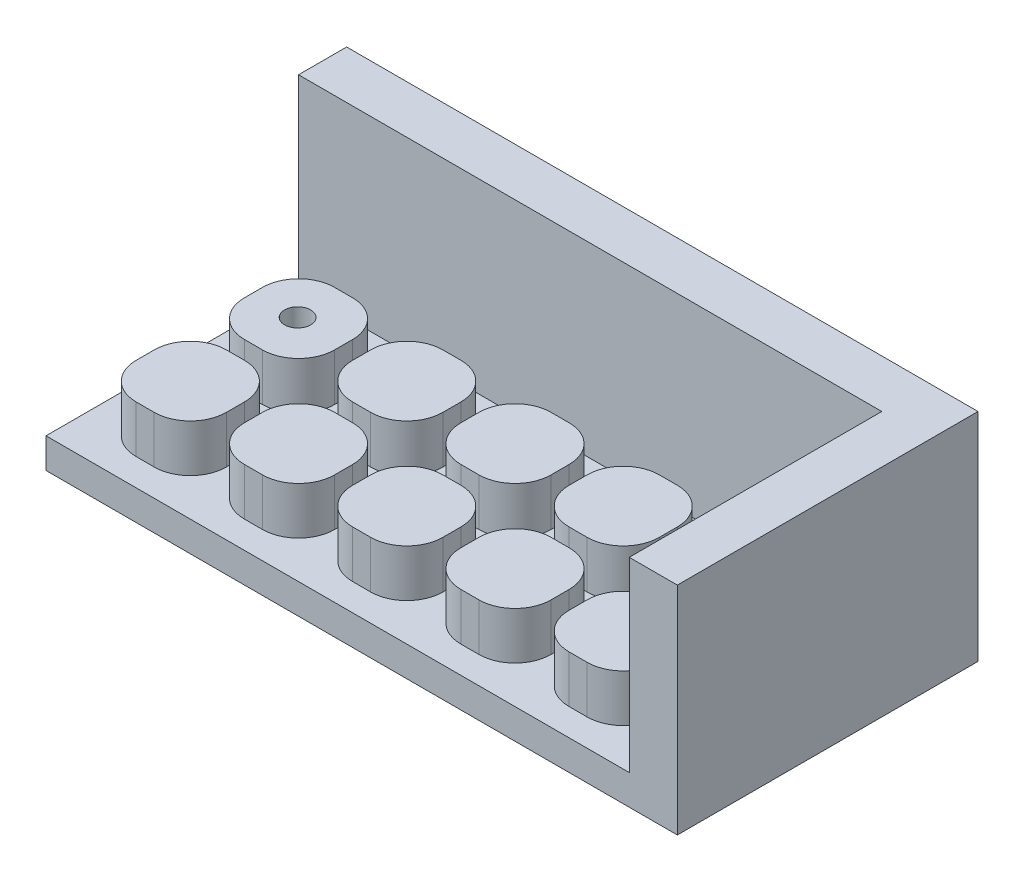
SolidWorks part; units mm, degrees
ref_plane "Front Plane" through (0, 0, 0) normal (0, 0, 1) x (1, 0, 0)
ref_plane "Top Plane" through (0, 0, 0) normal (0, 1, 0) x (1, 0, 0)
ref_plane "Right Plane" through (0, 0, 0) normal (1, 0, 0) x (0, 0, -1)
sketch "Sketch2" plane through (0, 0, 0) normal (0, 1, 0) x (1, 0, 0)
  line L0 (123.19, 0) -> (123.19, 53.34)
  line L1 (0, 0) -> (133.35, 0)
  line L2 (0, 0) -> (0, 63.5)
  line L3 (0, 63.5) -> (133.35, 63.5)
  line L4 (133.35, 0) -> (133.35, 63.5)
  line L5 (123.19, 53.34) -> (0, 53.34)
  line L6 (123.19, 63.5) -> (123.19, 53.34) construction
  line L7 (123.19, 53.34) -> (133.35, 53.34) construction
  dimension "D1" = 63.5
  dimension "D2" = 133.35
  dimension "D3" = 10.16
extrude "Boss-Extrude2" add sketch "Sketch2" along normal blind 6.35 contours L5 L0 L1 L4 L3 L2 | L0 L5 L2 L1 region at (61.595, 0, -26.67) region at (124.667, 0, -26.67)
extrude "Boss-Extrude3" add sketch "Sketch2<4>" along normal blind 45.72 contours L5 L0 L1 L4 L3 L2 region at (124.667, 0, -26.67)
sketch "Sketch2<4>" plane through (0, 0, 0) normal (0, 1, 0) x (1, 0, 0) same geometry as "Sketch2"
sketch "Sketch1" plane through (0, 6.35, 6.35) normal (0, 1, 0) x (1, 0, 0)
  line L1 (0, 6.35) -> (15.24, 6.35) construction
  line L2 (0, 6.35) -> (0, 21.59) construction
  line L3 (0, 21.59) -> (15.24, 21.59) construction
  line L4 (15.24, 6.35) -> (15.24, 21.59) construction
  line L5 (13.335, 31.115) -> (17.145, 31.115)
  line L6 (5.715, 23.495) -> (5.715, 19.685)
  line L7 (13.335, 12.065) -> (17.145, 12.065)
  line L8 (24.765, 23.495) -> (24.765, 19.685)
  line L9 (5.715, 31.115) -> (24.765, 12.065) construction
  line L10 (5.715, 12.065) -> (24.765, 31.115) construction
  arc A0 (17.145, 31.115) -> (24.765, 23.495) centre (17.145, 23.495) cw
  arc A1 (17.145, 12.065) -> (24.765, 19.685) centre (17.145, 19.685) ccw
  arc A2 (5.715, 19.685) -> (13.335, 12.065) centre (13.335, 19.685) ccw
  arc A3 (13.335, 31.115) -> (5.715, 23.495) centre (13.335, 23.495) ccw
  dimension "D1" = 7.62
  dimension "D2" = 15.24
  dimension "D3" = 19.05
extrude "Boss-Extrude1" add sketch "Sketch1" along normal blind 10
pattern_linear "LPattern1" count 5 spacing 22.86 along (1, 0, 0) count 2 spacing 22.86 along (0, 0, -1) of "Boss-Extrude1"
sketch "Sketch6" plane through (0, 16.35, 0) normal (0, 1, 0) x (1, 0, 0)
  circle A0 centre (106.3541, 38.2295) radius 2.75
  circle A1 centre (14.9141, 38.2295) radius 2.75
  dimension "D2" = 5.5
  dimension "D1" = 91.44
extrude "Cut-Extrude1" cut sketch "Sketch6" against normal blind 5.5
equation "\"D2@Sketch1\"=4 * \"channel size\""
equation "\"channel size\"= 0.15in"
equation "\"D3@Sketch1\"=5*\"channel size\""
equation "\"D1@Sketch1\"=2*\"channel size\""
equation "\"D3@LPattern1\"=6*\"channel size\""
equation "\"D4@LPattern1\"=6*\"channel size\""
equation "\"D1@Sketch6\"=24*\"channel size\""
